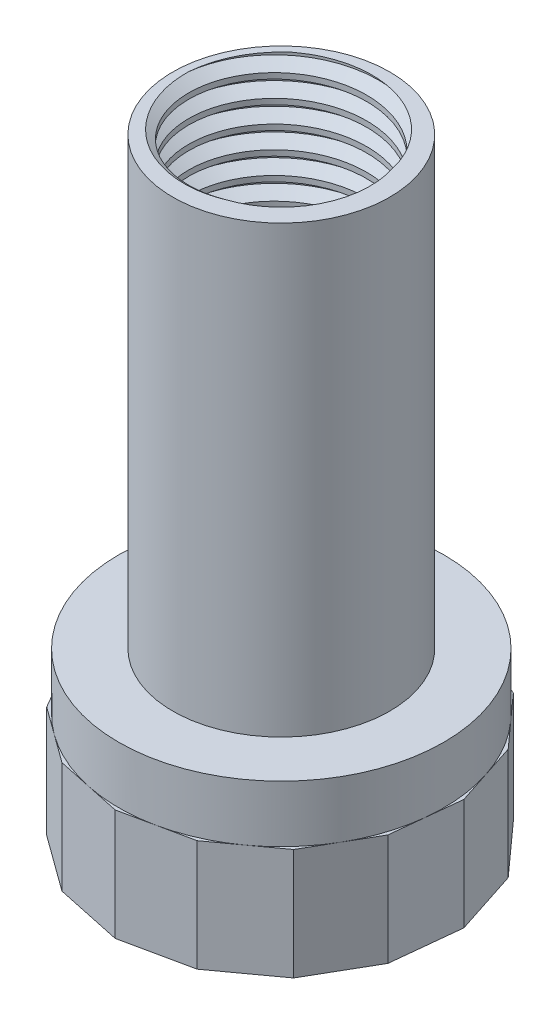
SolidWorks part; units mm, degrees
ref_plane "Front Plane" through (0, 0, 0) normal (0, 0, 1) x (1, 0, 0)
ref_plane "Top Plane" through (0, 0, 0) normal (0, 1, 0) x (1, 0, 0)
ref_plane "Right Plane" through (0, 0, 0) normal (1, 0, 0) x (0, 0, -1)
sketch "Sketch1" plane through (0, 0, 0) normal (0, 0, 1) x (1, 0, 0)
  line L0 (0, 0) -> (0, 55.1) construction
  line L1 (-14.6, 0) -> (-8, 0)
  line L2 (-8, 0) -> (0, 0) construction
  line L3 (-14.6, 0) -> (-14.6, 15.1)
  line L4 (-14.6, 15.1) -> (-9.75, 15.1)
  line L5 (-9.75, 15.1) -> (-9.75, 55.1)
  line L6 (-9.75, 55.1) -> (-8, 55.1)
  line L7 (-8, 55.1) -> (0, 55.1) construction
  line L8 (-8, 55.1) -> (-8, 0)
  line L9 (-14.6, 10) -> (-8, 10) construction
  line L10 (-9.75, 15.1) -> (-9.75, 0) construction
  dimension "D1" = 10
  dimension "D2" = 5.1
  dimension "D3" = 40
  dimension "D4" = 14.6
  dimension "D5" = 8
  dimension "D6" = 9.75
revolve "Revolve1" add sketch "Sketch1" angle 360 about L0 region at (-14.0451, 7.55, 0)
thread "Thread1" pitch 2 method cut profile "Thread Profile1" start angle 0, offset 2.5, length 65, pitch 2, diameter 16
ref_plane "Plane1" through (8, -2.5, 0) normal (0, 0, 1) x (1, 0, 0)
sketch "Thread Profile1" plane through (8, -2.5, 0) normal (0, 0, 1) x (1, 0, 0)
  line L0 (0, 0) -> (0, 2) construction
  line L1 (0, 0) -> (1.0825, 0.625)
  line L2 (1.0825, 0.625) -> (1.0825, 0.875)
  line L3 (1.0825, 0.875) -> (0, 1.5)
  line L4 (1.0825, 0.75) -> (0, 0.75) construction
  line L11 (0, 0) -> (0, 1.5)
  point P2 (0, 0)
  dimension "Pitch" = 2
  dimension "Profile_Angle" = 60
  dimension "Profile_Land" = 0.25
  dimension "Profile_Height" = 1.0825
sketch "Sketch5" plane through (0, 0, 0) normal (0, -1, 0) x (1, 0, 0)
  line L0 (-12.9264, -7.4631) -> (-8.7734, -12.0755)
  line L1 (6.071, 13.6357) -> (0, 14.9262)
  line L2 (0, 14.9262) -> (-6.071, 13.6357)
  line L3 (-6.071, 13.6357) -> (-11.0923, 9.9876)
  line L4 (-11.0923, 9.9876) -> (-14.1956, 4.6124)
  line L5 (-14.1956, 4.6124) -> (-14.8444, -1.5602)
  line L6 (-14.8444, -1.5602) -> (-12.9264, -7.4631)
  line L7 (-8.7734, -12.0755) -> (-3.1033, -14.6)
  line L8 (-3.1033, -14.6) -> (3.1033, -14.6)
  line L9 (3.1033, -14.6) -> (8.7734, -12.0755)
  line L10 (8.7734, -12.0755) -> (12.9264, -7.4631)
  line L11 (12.9264, -7.4631) -> (14.8444, -1.5602)
  line L12 (14.8444, -1.5602) -> (14.1956, 4.6124)
  line L13 (14.1956, 4.6124) -> (11.0923, 9.9876)
  line L14 (11.0923, 9.9876) -> (6.071, 13.6357)
  line L15 (0, 0) -> (0, 14.9262)
  circle A0 centre (0, 0) radius 14.6
  circle A1 centre (0, 0) radius 14.6 construction
  circle M17 centre (0, 0) radius 14.6
extrude "Boss-Extrude3" add sketch "Sketch5" against normal blind 10 contours L5 L6 M17 | L4 L5 M17 | L3 L4 M17 | L2 L3 M17 | L15 L1 M17 | L15 L2 M17 | L14 L1 M17 | L13 L14 M17 | L12 L13 M17 | L11 L12 M17 | L9 L10 M17 | L10 L11 M17 | L8 L9 M17 | L7 L8 M17 | L0 L7 M17 | L6 L0 M17 region at (-12.7012, 0, -7.3331) region at (-8.6205, 0, -11.8651) region at (-14.5858, 0, -1.533) region at (-3.0493, 0, -14.3456) region at (-13.9483, 0, 4.5321) region at (3.0493, 0, -14.3456) region at (-10.8991, 0, 9.8136) region at (8.6205, 0, -11.8651) region at (-5.9653, 0, 13.3982) region at (12.7012, 0, -7.3331) region at (-0.7622, 0, 14.6661) region at (14.5858, 0, -1.533) region at (0.7622, 0, 14.6661) region at (5.9653, 0, 13.3982) region at (13.9483, 0, 4.5321) region at (10.8991, 0, 9.8136)
